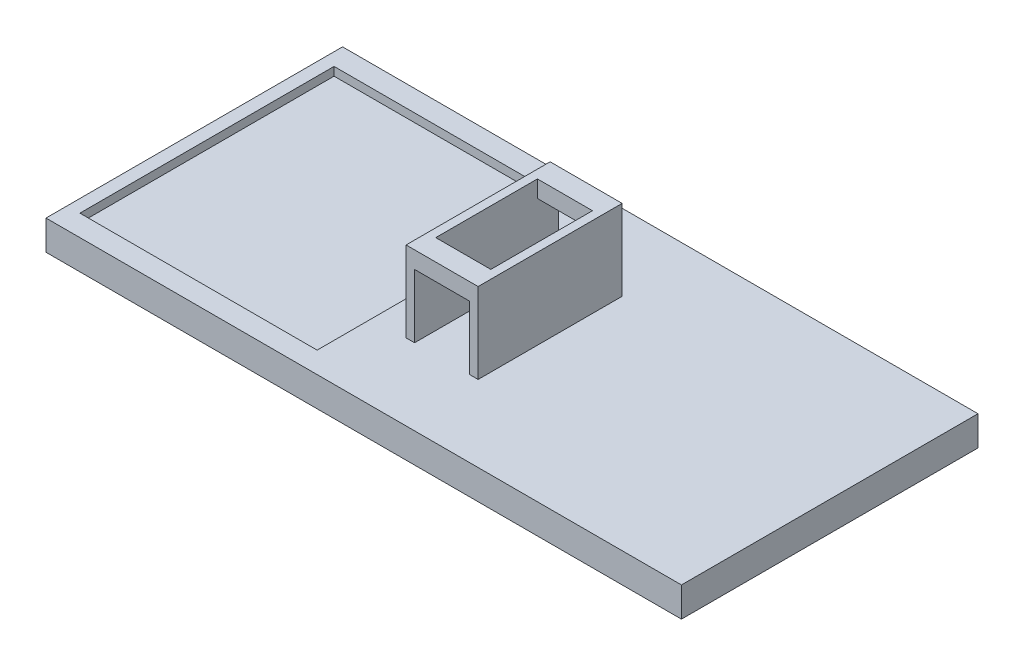
SolidWorks part; units mm, degrees
ref_plane "Спереди" through (0, 0, 0) normal (0, 0, 1) x (1, 0, 0)
ref_plane "Сверху" through (0, 0, 0) normal (0, 1, 0) x (1, 0, 0)
ref_plane "Справа" through (0, 0, 0) normal (1, 0, 0) x (0, 0, -1)
sketch "Эскиз2" plane through (0, 0, 0) normal (0, 1, 0) x (1, 0, 0)
  line L1 (0, 0) -> (150, 0)
  line L2 (0, 5) -> (0, 70)
  line L3 (0, 70) -> (150, 70)
  line L4 (150, 0) -> (150, 70)
  line L5 (0, 0) -> (0, 5)
  line L8 (3, 65) -> (59, 65)
  line L9 (3, 65) -> (3, 5)
  line L10 (3, 5) -> (59, 5)
  line L11 (59, 65) -> (59, 5)
extrude "Бобышка-Вытянуть3" add sketch "Эскиз2" along normal blind 5 contours L1 L4 L3 L2 L5
sketch "Эскиз4" plane through (0, 5, 0) normal (0, 1, 0) x (1, 0, 0)
  line L5 (3, 65) -> (59, 65)
  line L6 (3, 65) -> (3, 5)
  line L7 (3, 5) -> (59, 5)
  line L8 (59, 65) -> (59, 5)
extrude "Бобышка-Вытянуть4" add sketch "Эскиз2<6>" along normal blind 7
sketch "Эскиз2<6>" plane through (0, 0, 0) normal (0, 1, 0) x (1, 0, 0) same geometry as "Эскиз2"
extrude "Бобышка-Вытянуть5" add sketch "Эскиз4" against normal blind 5 contours L8 L7 L6 L5
sketch "Эскиз5" plane through (0, 7, 0) normal (0, 1, 0) x (1, 0, 0)
  line L1 (69, 52) -> (67, 52)
  line L4 (69, 35) -> (69, 23)
  line L5 (69, 23) -> (82, 23)
  line L6 (82, 35) -> (82, 23)
  line L8 (69, 35) -> (69, 47)
  line L9 (69, 47) -> (82, 47)
  line L10 (82, 35) -> (82, 47)
  line L11 (67, 52) -> (84, 52)
  line L12 (67, 52) -> (67, 18)
  line L13 (67, 18) -> (84, 18)
  line L14 (84, 52) -> (84, 18)
extrude "Бобышка-Вытянуть6" add sketch "Эскиз5" along normal blind 19 contours L14 L11 L1 L12 L13 L10 L6 L5 L4 L8 L9 region at (76.5, 7, -51.6199)
sketch "Эскиз7" plane through (0, 0, -18) normal (0, 0, 1) x (1, 0, 0)
  line L1 (67, 7) -> (84, 7) construction
  line L3 (69, 7) -> (82, 7)
  line L4 (69, 7) -> (69, 22)
  line L5 (69, 22) -> (82, 22)
  line L6 (82, 7) -> (82, 22)
extrude "Вырез-Вытянуть1" cut sketch "Эскиз7" against normal blind 34
